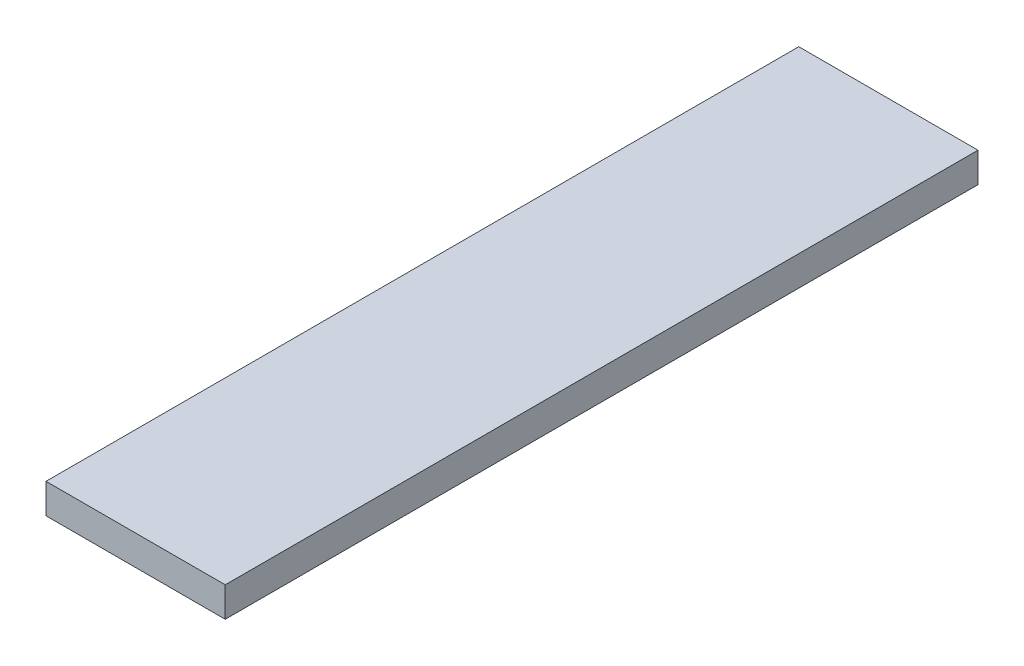
SolidWorks part; units mm, degrees
ref_plane "Front Plane" through (0, 0, 0) normal (0, 0, 1) x (1, 0, 0)
ref_plane "Top Plane" through (0, 0, 0) normal (0, 1, 0) x (1, 0, 0)
ref_plane "Right Plane" through (0, 0, 0) normal (1, 0, 0) x (0, 0, -1)
sketch "Sketch1" plane through (0, 0, 0) normal (0, 1, 0) x (1, 0, 0)
  line L1 (-80.6509, 30.6509) -> (-50.6509, 30.6509)
  line L2 (-80.6509, 30.6509) -> (-80.6509, -95.3491)
  line L3 (-80.6509, -95.3491) -> (-50.6509, -95.3491)
  line L4 (-50.6509, 30.6509) -> (-50.6509, -95.3491)
  dimension "D1" = 30
  dimension "D2" = 126
extrude "Boss-Extrude1" add sketch "Sketch1" along normal blind 5
